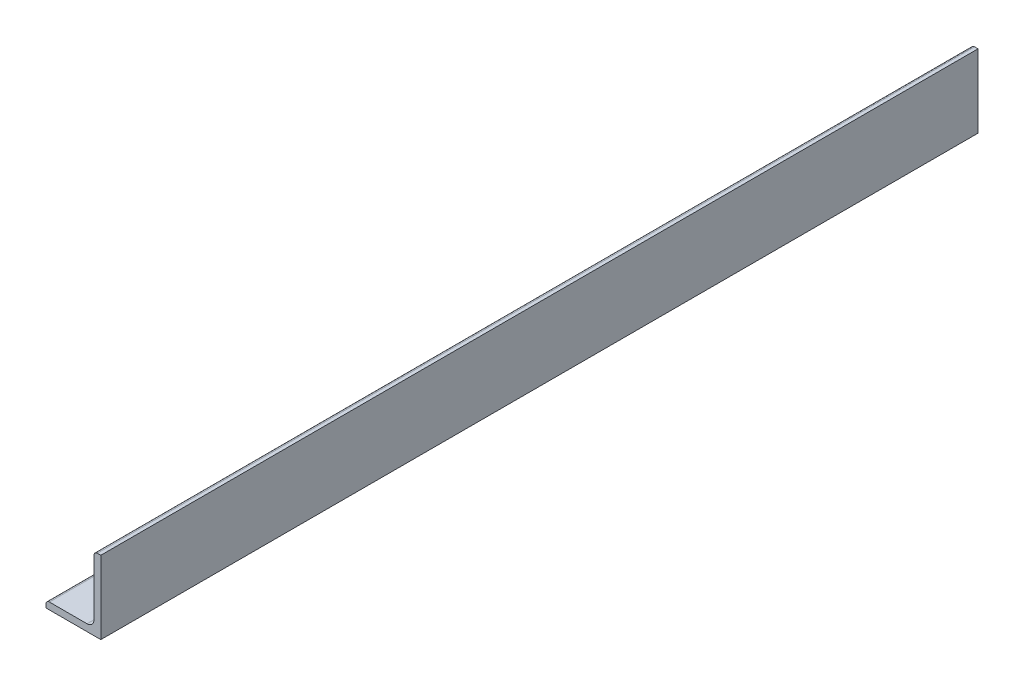
SolidWorks part; units mm, degrees
material "6061-T6 (SS)"
ref_plane "Front Plane" through (0, 0, 0) normal (0, 0, 1) x (1, 0, 0)
ref_plane "Top Plane" through (0, 0, 0) normal (0, 1, 0) x (1, 0, 0)
ref_plane "Right Plane" through (0, 0, 0) normal (1, 0, 0) x (0, 0, -1)
sketch "Sketch0" plane through (0, 0, 0) normal (0, 0, 1) x (1, 0, 0)
  line L0 (-19.05, -25.4) -> (19.05, -25.4)
  line L1 (19.05, -25.4) -> (19.05, 25.4)
  line L2 (19.05, 0) -> (0, 0) construction
  line L3 (0, 0) -> (0, -25.4) construction
  line L4 (14.2748, -15.8496) -> (14.2748, 25.4) construction
  line L5 (9.4996, -20.6248) -> (-19.05, -20.6248) construction
  arc A0 (14.2748, -15.8496) -> (9.4996, -20.6248) centre (9.4996, -15.8496) cw
  point P3 (12.8762, -19.2262)
  dimension "Inside Corner Radius" = 4.7752
  dimension "Outside Height" = 50.8
  dimension "Inside Height" = 46.0248
  dimension "Inside Width" = 33.3248
  dimension "Wall Thickness" = 4.7752
  dimension "D1" = 4.7752
  dimension "Outside Width" = 38.1
sketch "Sketch1" plane through (0, 0, 0) normal (1, 0, 0) x (0, 0, -1)
  line L0 (304.8, 0) -> (-304.8, 0)
  point P4 (0, 0)
  dimension "Length" = 609.6
sketch "Sketch2" plane through (0, 0, 0) normal (0, 0, 1) x (1, 0, 0)
  line L0 (-19.05, -25.4) -> (19.05, -25.4)
  line L1 (19.05, -25.4) -> (19.05, 25.4)
  line L2 (19.05, 25.4) -> (14.2748, 25.4) construction
  line L3 (14.2748, 23.0124) -> (14.2748, -15.8496)
  line L4 (9.4996, -20.6248) -> (-16.6624, -20.6248)
  line L5 (-19.05, -25.4) -> (-19.05, -20.6248) construction
  line L6 (16.6624, 25.4) -> (19.05, 25.4)
  line L7 (-19.05, -23.0124) -> (-19.05, -25.4)
  line L8 (19.05, 0) -> (0, 0) construction
  line L9 (0, 0) -> (0, -25.4) construction
  arc A0 (14.2748, 23.0124) -> (16.6624, 25.4) centre (16.6624, 23.0124) cw
  arc A1 (-19.05, -23.0124) -> (-16.6624, -20.6248) centre (-16.6624, -23.0124) cw
  arc A2 (14.2748, -15.8496) -> (9.4996, -20.6248) centre (9.4996, -15.8496) cw
  dimension "Inside Radius" = 4.7752
  dimension "Height" = 50.8
  dimension "Width" = 38.1
  dimension "Thickness" = 4.7752
extrude "Boss-Extrude1" add sketch "Sketch2" along normal mid plane 609.6
sketch "Break Locations" plane through (0, 0, 0) normal (1, 0, 0) x (0, 0, -1)
  line L0 (-252.984, 0) -> (252.984, 0)
  line L1 (-304.8, -25.4) -> (-304.8, 25.4) construction
  line L2 (304.8, -25.4) -> (304.8, 25.4) construction
  point P0 (-261.62, 0)
  point P1 (261.62, 0)
  point P10 (0, 0)
  point P11 (252.984, 0)
  point P13 (-252.984, 0)
  dimension "D1" = 43.18
  dimension "D2" = 43.18
  dimension "D3" = 51.816
equation "\"D1@Break Locations\" = .85 * \"Height@Sketch2\""
equation "\"D2@Break Locations\"=\"D1@Break Locations\""
equation "\"Thickness@Sketch2\" = \"Wall Thickness@Sketch0\""
equation "\"Height@Sketch2\" = \"Outside Height@Sketch0\""
equation "\"Width@Sketch2\" = \"Outside Width@Sketch0\""
equation "\"Inside Radius@Sketch2\" = \"Inside Corner Radius@Sketch0\""
equation "\"Length@Boss-Extrude1\" = \"Length@Sketch1\""
equation "\"D3@Break Locations\"=\"D2@Break Locations\"*1.2"
equation "\"D1@Sketch0\"=\"Wall Thickness@Sketch0\""
